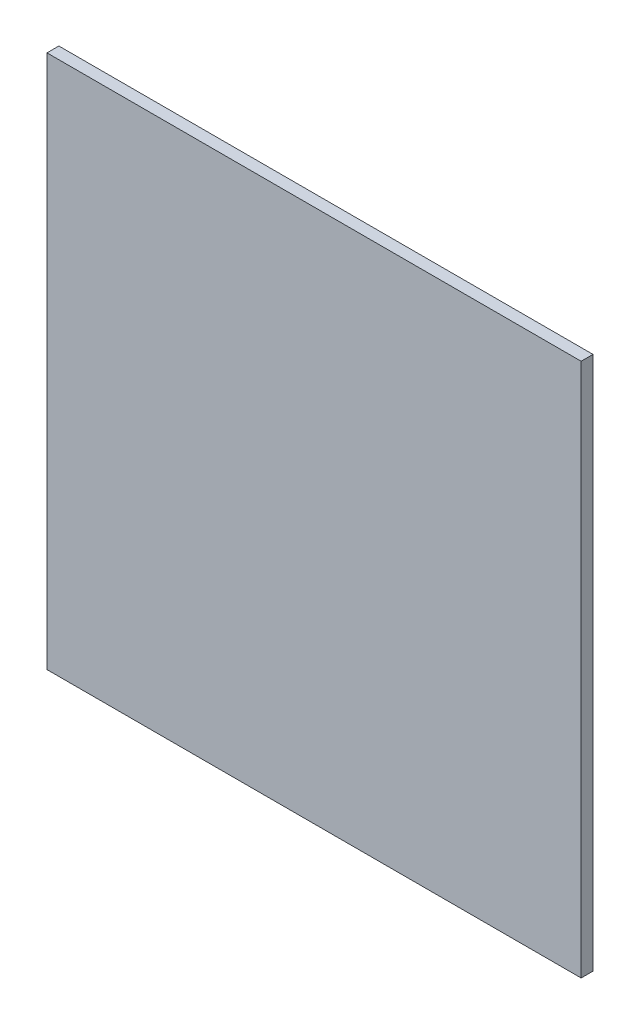
SolidWorks part; units mm, degrees
material "Fibra de vidrio-E"
ref_plane "Alzado" through (0, 0, 0) normal (0, 0, 1) x (1, 0, 0)
ref_plane "Planta" through (0, 0, 0) normal (0, 1, 0) x (1, 0, 0)
ref_plane "Vista lateral" through (0, 0, 0) normal (1, 0, 0) x (0, 0, -1)
sketch "Croquis1" plane through (0, 0, 0) normal (0, 0, 1) x (1, 0, 0)
  line L1 (0, 0) -> (130, 0)
  line L2 (0, 0) -> (0, 70)
  line L3 (0, 70) -> (130, 70)
  line L4 (130, 0) -> (130, 70)
  dimension "D1" = 70
  dimension "D2" = 130
extrude "Saliente-Extruir1" add sketch "Croquis1" along normal blind 2
sketch "Croquis2" plane through (0, 0, 0) normal (0, 0, -1) x (-1, 0, 0)
  line L2 (-130, 70) -> (0, 70) construction
  line L3 (-130, 0) -> (-90, 0)
  line L4 (-130, 0) -> (-130, 70)
  line L5 (-130, 70) -> (-90, 70)
  line L6 (-90, 0) -> (-90, 70)
  dimension "D1" = 40
extrude "Cortar-Extruir1" cut sketch "Croquis2" against normal through all
sketch "Croquis4" plane through (0, 0, 0) normal (0, 0, -1) x (-1, 0, 0)
  line L1 (0, 70) -> (-90, 70)
  line L2 (0, 70) -> (0, 80)
  line L3 (0, 80) -> (-90, 80)
  line L4 (-90, 70) -> (-90, 80)
  line L5 (0, 0) -> (-90, 0)
  line L6 (0, 0) -> (0, -10)
  line L7 (0, -10) -> (-90, -10)
  line L8 (-90, 0) -> (-90, -10)
  point P10 (0, 75)
  dimension "D1" = 90
  dimension "D2" = 90
  dimension "D3" = 10
  dimension "D4" = 10
extrude "Saliente-Extruir2" add sketch "Croquis4" against normal through all
